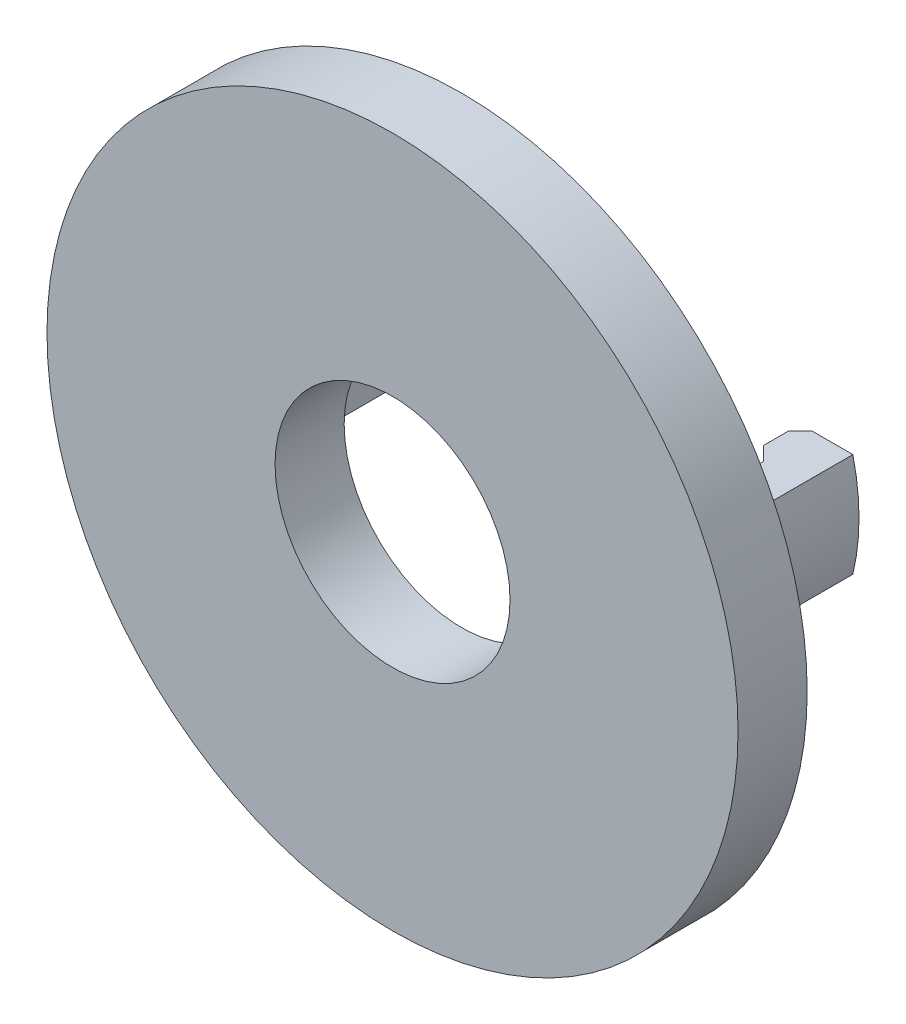
SolidWorks part; units mm, degrees
ref_plane "Front" through (0, 0, 0) normal (0, 0, 1) x (1, 0, 0)
ref_plane "Top" through (0, 0, 0) normal (0, 1, 0) x (1, 0, 0)
ref_plane "Right" through (0, 0, 0) normal (1, 0, 0) x (0, 0, -1)
sketch "Guard base" plane through (0, 0, 0) normal (0, 0, 1) x (1, 0, 0)
  circle A0 centre (0, 0) radius 25
  dimension "D1" = 50
extrude "Guard" add sketch "Guard base" along normal blind 5
sketch "Inner axle hole base" plane through (0, 0, 5) normal (0, 0, 1) x (1, 0, 0)
  circle A0 centre (0, 0) radius 8.5
  dimension "D1" = 17
extrude "Inner axle hole" cut sketch "Inner axle hole base" against normal through all
sketch "Coupling tooth base" plane through (0, 0, 0) normal (0, 1, 0) x (1, 0, 0)
  line L0 (10, 0) -> (15.5, 0) construction
  line L1 (15.5, 0) -> (15.5, 13)
  line L2 (12.5, 2.5) -> (12.5, 9) construction
  line L3 (15.5, 13) -> (12.5, 13) construction
  line L4 (12.5, 13) -> (11.5, 12) construction
  line L5 (11.5, 10) -> (12.5, 9) construction
  line L6 (16, 12.75) -> (16, 0)
  line L7 (12.75, 9.1036) -> (12.75, 2.3964)
  line L8 (12.5, 2.5) -> (10, 0) construction
  line L9 (12.75, 9.1036) -> (11.75, 10.1036)
  line L10 (11.5, 12) -> (11.5, 10) construction
  line L11 (11.75, 10.1036) -> (11.75, 11.8964)
  line L12 (15.5, 0) -> (15.5, 12.75) construction
  line L13 (15.5, 0) -> (10.3536, 0)
  line L14 (12.75, 2.3964) -> (10.3536, 0)
  line L15 (11.75, 11.8964) -> (12.6036, 12.75)
  line L16 (12.6036, 12.75) -> (15.5, 12.75)
  line L17 (15.5, 12.75) -> (25, 12.75)
  line L18 (25, 12.75) -> (25, 0)
  line L19 (25, 0) -> (15.5, 0)
  point P24 (8.5, 0)
  dimension "D2" = 1
  dimension "D3" = 4
  dimension "D4" = 13
  dimension "D5" = 4
  dimension "D6" = 0.25
  dimension "D7" = 0.25
  dimension "D8" = 0.25
  dimension "D9" = 0.25
  dimension "D10" = 225
  dimension "D11" = 5.5
  dimension "D12" = 0.25
  dimension "D13" = 135
  dimension "D14" = 0.25
  dimension "D15" = 0.5
  dimension "D16" = 1.5
extrude "Coupling tooth" add sketch "Coupling tooth base" along normal blind 3.75 and the other way blind 3.75 contours L16 L15 L11 L9 L7 L14 L13 L1 | L19 L6 L17 L1 region at (13.8475, 0, -6.2973) region at (15.75, 0, -6.375)
ref_axis "Center Z" through (0, 0, 0) along (0, 0, -1)
revolve "Circularity cut" cut sketch "Sketch6<4>" angle 360 about axis through (0, 0, 0) along (0, 0, -1) region at (20.5, 0, -6.375)
sketch "Sketch6<4>" plane through (0, 0, 0) normal (0, 1, 0) x (1, 0, 0) same geometry as "Coupling tooth base"
mirror "Coutpling teeth" about plane through (0, 0, 0) normal (1, 0, 0) of "Coupling tooth", "Circularity cut"
equation "\"mate_room\"= 0.25"
equation "\"D6@Coupling tooth base\"=\"mate_room\""
equation "\"D8@Coupling tooth base\"=\"mate_room\""
equation "\"D7@Coupling tooth base\"=\"mate_room\""
equation "\"D9@Coupling tooth base\"=\"mate_room\""
equation "\"D12@Coupling tooth base\"=\"mate_room\""
equation "\"D14@Coupling tooth base\"=\"mate_room\""
equation "\"removal_room\"= 0.75"
equation "\"D1@Inner axle hole base\" = \"small_inner_axle_diameter\""
equation "\"guard_thickness\"=5"
equation "\"spool_inner_diameter_room\"=1"
equation "\"32_92_coupling_tooth_height\"=13"
equation "\"32_92_coupling_tooth_thickness_total\"=4"
equation "\"32_92_coupling_tooth_protrusion\"=1"
equation "\"32_92_coupling_tooth_depth\"=8"
equation "\"32_92_coupling_tooth_base_thickness\"=5.5"
equation "\"D1@Guard\"=\"guard_thickness\""
equation "\"32_92_guard_diameter\"=50"
equation "\"D1@Guard base\"=\"32_92_guard_diameter\""
equation "\"D4@Coupling tooth base\"=\"32_92_coupling_tooth_height\""
equation "\"D3@Coupling tooth base\"=\"32_92_coupling_tooth_thickness_total\""
equation "\"D2@Coupling tooth base\"=\"32_92_coupling_tooth_protrusion\""
equation "\"D11@Coupling tooth base\"=\"32_92_coupling_tooth_base_thickness\""
equation "\"32_92_coupling_tooth_head_height\"=4"
equation "\"D5@Coupling tooth base\"=\"32_92_coupling_tooth_head_height\""
equation "\"32_92_spool_inner_diameter\"=32"
equation "\"32_92_spool_thickness\"=92"
equation "\"small_inner_axle_diameter\"=17"
equation "\"D16@Coupling tooth base\" = ( \"large_inner_axle_diameter\" - \"small_inner_axle_diameter\" ) / 2"
equation "\"large_inner_axle_diameter\"=20"
equation "\"D1@Coupling tooth\"=\"32_92_coupling_tooth_depth\"/2 - \"mate_room\""
equation "\"D2@Coupling tooth\"=\"32_92_coupling_tooth_depth\"/2 - \"mate_room\""
